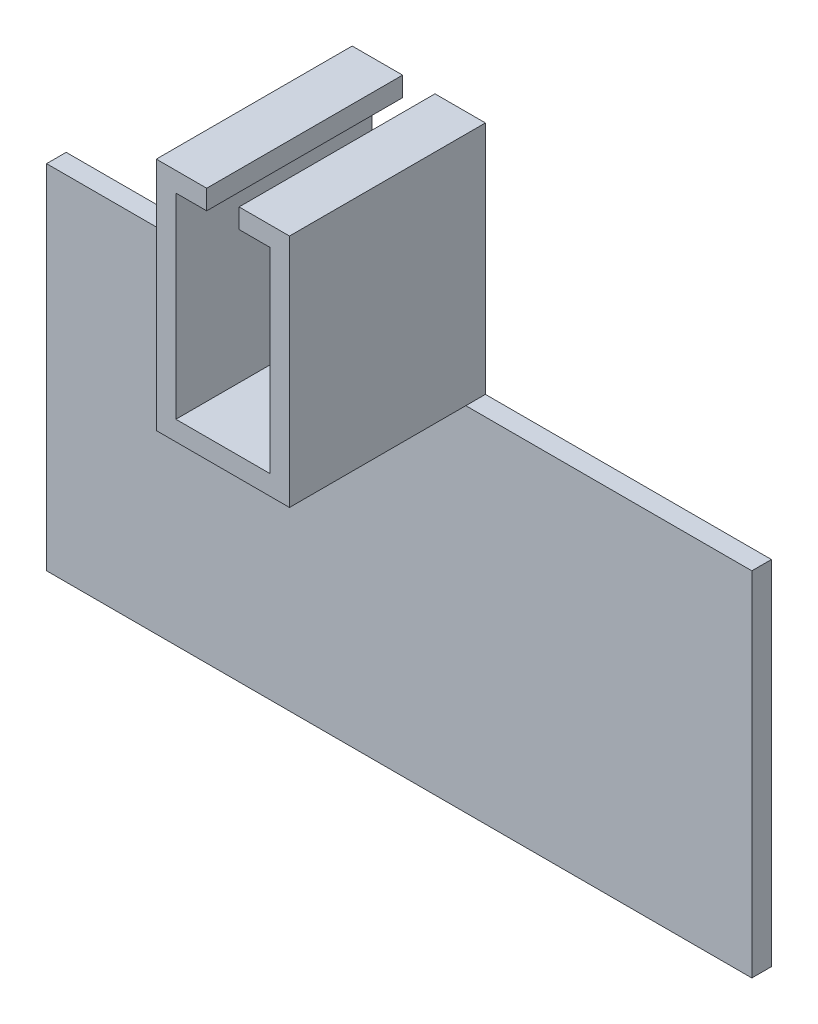
SolidWorks part; units mm, degrees
ref_plane "Ebene vorne" through (0, 0, 0) normal (0, 0, 1) x (1, 0, 0)
ref_plane "Ebene oben" through (0, 0, 0) normal (0, 1, 0) x (1, 0, 0)
ref_plane "Ebene rechts" through (0, 0, 0) normal (1, 0, 0) x (0, 0, -1)
sketch "Skizze1" plane through (0, 0, 0) normal (0, 0, 1) x (1, 0, 0)
  line L0 (-120, 0) -> (120, 0)
  line L1 (120, 0) -> (120, 500)
  line L2 (120, 500) -> (41.3483, 500)
  line L3 (41.3483, 500) -> (41.3483, 550)
  line L4 (41.3483, 550) -> (170, 550)
  line L5 (170, 550) -> (170, -50)
  line L6 (900, -50) -> (900, -950)
  line L7 (900, -950) -> (513.4831, -950)
  line L8 (170, -50) -> (900, -50)
  line L9 (0, -322.4719) -> (0, 738.2022) construction
  line L10 (513.4831, -950) -> (-513.4831, -950)
  line L11 (-170, -50) -> (-900, -50)
  line L12 (-900, -950) -> (-513.4831, -950)
  line L13 (-900, -50) -> (-900, -950)
  line L14 (-170, 550) -> (-170, -50)
  line L15 (-41.3483, 550) -> (-170, 550)
  line L16 (-41.3483, 500) -> (-41.3483, 550)
  line L17 (-120, 500) -> (-41.3483, 500)
  line L18 (-120, 0) -> (-120, 500)
  point P15 (0, -950)
  point P23 (0, 0)
  dimension "D1" = 500
  dimension "D2" = 120
  dimension "D3" = 50
  dimension "D4" = 50
  dimension "D5" = 50
  dimension "D6" = 900
  dimension "D7" = 900
extrude "Aufsatz-Linear austragen1" add sketch "Skizze1" along normal blind 500
sketch "Skizze2" plane through (900, 0, 0) normal (1, 0, 0) x (0, 0, -1)
  line L0 (-500, -50) -> (0, -50) construction
  line L1 (-500, -50) -> (-50, -50)
  line L2 (-500, -50) -> (-500, -950)
  line L3 (-500, -950) -> (-50, -950)
  line L4 (-50, -50) -> (-50, -950)
  line L5 (-500, -950) -> (-500, -50) construction
  line L6 (-500, -950) -> (0, -950) construction
  dimension "D1" = 450
extrude "Schnitt-Linear austragen1" cut sketch "Skizze2" against normal through all
